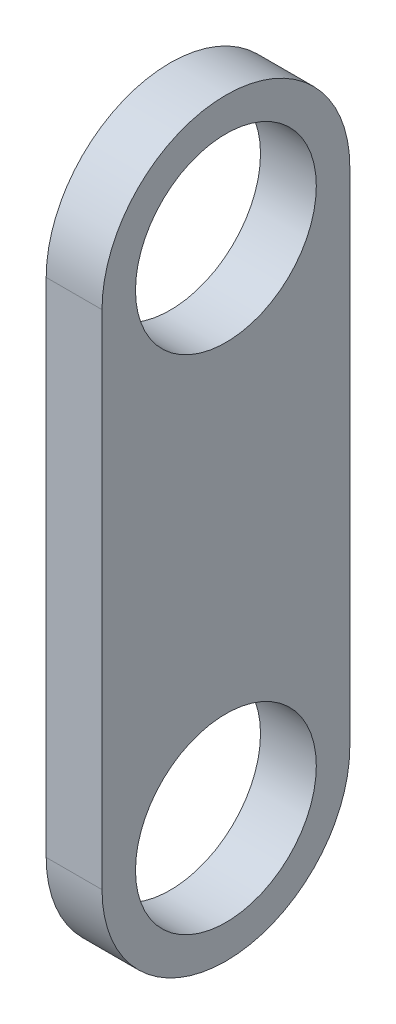
SolidWorks part; units mm, degrees
ref_plane "Front Plane" through (0, 0, 0) normal (1, 0, 0) x (0, 1, 0)
ref_plane "Top Plane" through (0, 0, 0) normal (0, 0, 1) x (0, 1, 0)
ref_plane "Right Plane" through (0, 0, 0) normal (0, 1, 0) x (-1, 0, 0)
sketch "Sketch2" plane through (0, 0, 0) normal (1, 0, 0) x (0, 1, 0)
  line L0 (0, 0) -> (8.1, 0)
  line L1 (0, 11.1) -> (45, 11.1)
  line L2 (0, -11.1) -> (45, -11.1)
  line L3 (36.9, 0) -> (45, 0)
  circle A0 centre (0, 0) radius 8.1
  circle A1 centre (45, 0) radius 8.1
  arc A2 (0, 11.1) -> (0, -11.1) centre (0, 0) ccw
  arc A3 (45, -11.1) -> (45, 11.1) centre (45, 0) ccw
  circle A4 centre (0, 0) radius 11.1 construction
  circle A5 centre (45, 0) radius 11.1 construction
  dimension "D1" = 16.2
  dimension "D2" = 16.2
  dimension "D5" = 45
  dimension "D3" = 3
extrude "Boss-Extrude1" add sketch "Sketch2" along normal mid plane 5 contours L2 A3 L1 A2 A0 A1 region at (0, 22.5, 0)
sketch "Sketch3" plane through (-2.5, 0, 0) normal (1, 0, 0) x (0, 1, 0)
  circle A0 centre (0, 0) radius 4.25
  dimension "D1" = 8.5
extrude "Cut-Extrude1" [suppressed] cut sketch "Sketch3" along normal blind 0.8
